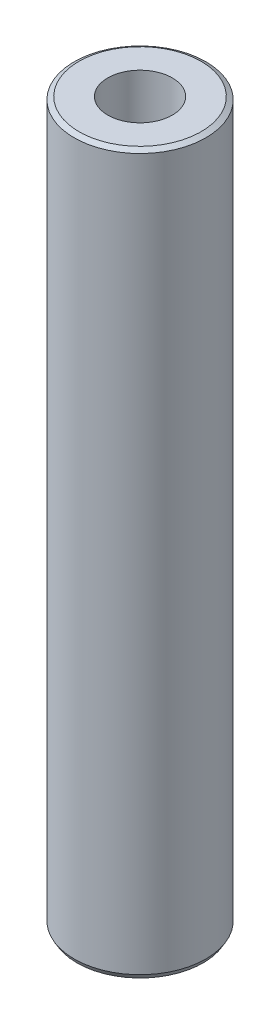
SolidWorks part; units mm, degrees
ref_plane "Front Plane" through (0, 0, 0) normal (0, 0, 1) x (1, 0, 0)
ref_plane "Top Plane" through (0, 0, 0) normal (0, 1, 0) x (1, 0, 0)
ref_plane "Right Plane" through (0, 0, 0) normal (1, 0, 0) x (0, 0, -1)
sketch "Sketch1" plane through (0, 0, 0) normal (0, 1, 0) x (1, 0, 0)
  circle A0 centre (0, 0) radius 55
  dimension "SHAFT_OD" = 110
extrude "Boss-Extrude1" add sketch "Sketch1" along normal blind 600
sketch "Sketch2" plane through (0, 0, 0) normal (0, 1, 0) x (1, 0, 0)
  circle A0 centre (0, 0) radius 26.9493
  dimension "BORE_D" = 53.8986
extrude "Cut-Extrude1" cut sketch "Sketch2" along normal through all
chamfer "Chamfer1" distance 2.3408 angle 60 2 edges at (0, 600, 55) (0, 0, 55) first distance on face at (0, 600, 55) first distance on face at (0, 0, 26.9493)
